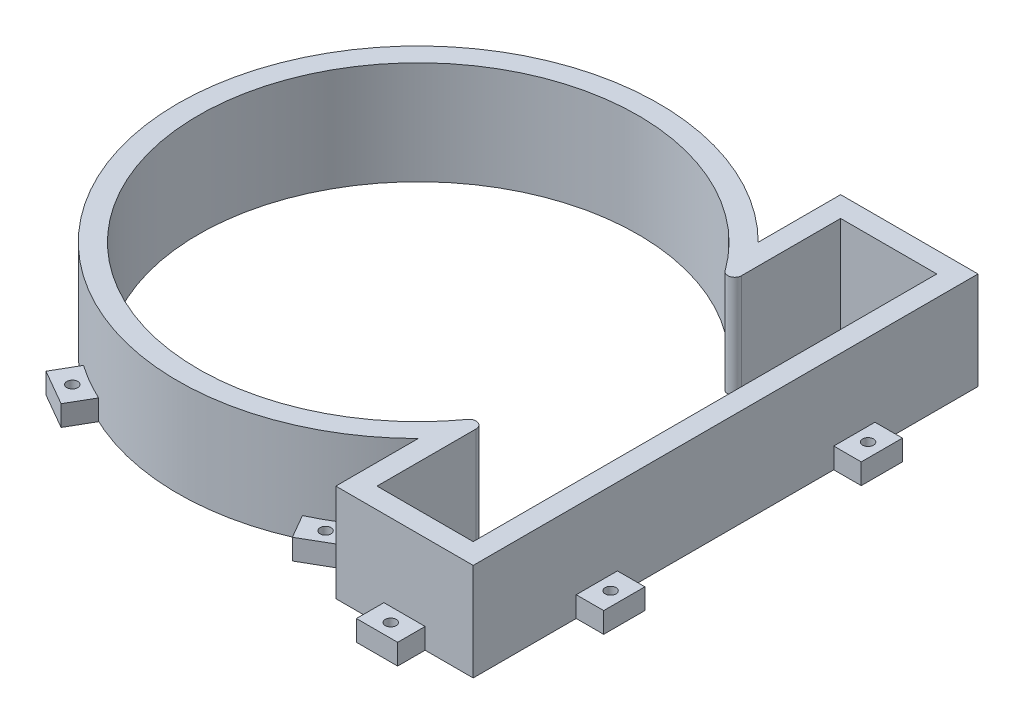
SolidWorks part; units mm, degrees
ref_plane "Front Plane" through (0, 0, 0) normal (0, 0, 1) x (1, 0, 0)
ref_plane "Top Plane" through (0, 0, 0) normal (0, 1, 0) x (1, 0, 0)
ref_plane "Right Plane" through (0, 0, 0) normal (1, 0, 0) x (0, 0, -1)
sketch "Sketch1" plane through (0, 0, 0) normal (0, 1, 0) x (1, 0, 0)
  line L0 (24.7487, 24.7487) -> (24.7487, 36.7487)
  line L1 (50, 50) -> (-50, 50) construction
  line L2 (50, 50) -> (50, -50) construction
  line L3 (50, -50) -> (-50, -50) construction
  line L4 (-50, 50) -> (-50, -50) construction
  line L5 (50, 50) -> (-50, -50) construction
  line L6 (50, -50) -> (-50, 50) construction
  line L7 (24.7487, 36.7487) -> (44.7487, 36.7487)
  line L8 (44.7487, 36.7487) -> (44.7487, -36.7487)
  line L9 (0, 0) -> (50, 0) construction
  line L10 (24.7487, -36.7487) -> (44.7487, -36.7487)
  line L11 (24.7487, -24.7487) -> (24.7487, -36.7487)
  line L12 (27.7487, -15.9376) -> (27.7487, -33.7487)
  line L13 (27.7487, -33.7487) -> (41.7487, -33.7487)
  line L14 (41.7487, 33.7487) -> (41.7487, -33.7487)
  line L15 (27.7487, 33.7487) -> (41.7487, 33.7487)
  line L16 (27.7487, 15.9376) -> (27.7487, 33.7487)
  arc A1 (24.7487, 24.7487) -> (24.7487, -24.7487) centre (0, 0) ccw
  arc A4 (27.7487, 15.9376) -> (27.7487, -15.9376) centre (0, 0) ccw
  point P0 (0, 0)
  point P13 (44.7487, 0)
  dimension "D3" = 70
  dimension "D6" = 3
  dimension "D1" = 100
  dimension "D2" = 100
  dimension "D4" = 12
  dimension "D5" = 20
extrude "Boss-Extrude1" add sketch "Sketch1" along normal blind 15
chamfer "Chamfer13" distance 3 angle 15 6 edges at (24.7487, 0, -30.7487) (34.7487, 0, -36.7487) (44.7487, 0, 0) (34.7487, 0, 36.7487) (24.7487, 0, 30.7487) (-35, 0, 0) first distance on face at (21.4573, 0, 0)
ref_plane "Plane3" through (0, 0.8038, 0) normal (0, -1, 0) x (-1, 0, 0)
sketch "Sketch6" plane through (0, 0.8038, 0) normal (0, -1, 0) x (-1, 0, 0)
  line L0 (-48.1424, 0) -> (38.8712, 0) construction
  line L1 (34.8712, -3) -> (38.8712, -3)
  line L2 (38.8712, -3) -> (38.8712, 3)
  line L3 (34.8712, 3) -> (38.8712, 3)
  line L4 (14.8375, -31.6993) -> (16.8375, -35.1634)
  line L5 (16.8375, -35.1634) -> (22.0337, -32.1634)
  line L6 (20.0337, -28.6993) -> (22.0337, -32.1634)
  line L7 (-20.0337, -28.6993) -> (-22.0337, -32.1634)
  line L8 (-22.0337, -32.1634) -> (-16.8375, -35.1634)
  line L9 (-14.8375, -31.6993) -> (-16.8375, -35.1634)
  line L10 (-34.7487, -36.7487) -> (-34.7487, -40.7487) construction
  line L11 (-24.7487, -36.7487) -> (-44.7487, -36.7487) construction
  line L12 (-44.7487, -18.7487) -> (-48.7487, -18.7487) construction
  line L13 (-14.8375, 31.6993) -> (-16.8375, 35.1634)
  line L14 (-16.8375, 35.1634) -> (-22.0337, 32.1634)
  line L15 (-20.0337, 28.6993) -> (-22.0337, 32.1634)
  line L16 (20.0337, 28.6993) -> (22.0337, 32.1634)
  line L17 (22.0337, 32.1634) -> (16.8375, 35.1634)
  line L18 (14.8375, 31.6993) -> (16.8375, 35.1634)
  line L19 (-34.8712, -3) -> (-38.8712, -3) [skipped]
  line L20 (-38.8712, 3) -> (-38.8712, 0) [skipped]
  line L21 (-34.8712, 3) -> (-38.8712, 3) [skipped]
  line L22 (-44.7487, -36.7487) -> (-44.7487, 36.7487) construction
  line L23 (-31.7487, -36.7487) -> (-31.7487, -40.7487)
  line L24 (-31.7487, -40.7487) -> (-37.7487, -40.7487)
  line L25 (-37.7487, -36.7487) -> (-37.7487, -40.7487)
  line L26 (-44.7487, -21.7487) -> (-48.7487, -21.7487)
  line L27 (-48.7487, -21.7487) -> (-48.7487, -15.7487)
  line L28 (-44.7487, -15.7487) -> (-48.7487, -15.7487)
  line L29 (-31.7487, -36.7487) -> (-37.7487, -36.7487)
  line L30 (-44.7487, -21.7487) -> (-44.7487, -15.7487)
  line L31 (-44.7487, 15.7487) -> (-48.7487, 15.7487)
  line L32 (-48.7487, 21.7487) -> (-48.7487, 15.7487)
  line L33 (-44.7487, 21.7487) -> (-44.7487, 15.7487)
  line L34 (-44.7487, 21.7487) -> (-48.7487, 21.7487)
  line L35 (-31.7487, 36.7487) -> (-37.7487, 36.7487)
  line L36 (-37.7487, 36.7487) -> (-37.7487, 40.7487)
  line L37 (-31.7487, 40.7487) -> (-37.7487, 40.7487)
  line L38 (-31.7487, 36.7487) -> (-31.7487, 40.7487)
  arc A0 (-20.0337, -28.6993) -> (-14.8375, -31.6993) centre (0, 0) ccw
  arc A1 (-24.7487, -24.7487) -> (-24.7487, 24.7487) centre (0, 0) ccw construction
  circle A2 centre (36.8712, 0) radius 0.795
  circle A3 centre (18.4356, -31.9314) radius 0.795
  circle A4 centre (-18.4356, -31.9314) radius 0.795
  circle A6 centre (-18.4356, 31.9314) radius 0.795
  circle A7 centre (18.4356, 31.9314) radius 0.795
  arc A8 (-37.6662, 0) -> (-36.0762, 0) centre (-36.8712, 0) ccw [skipped]
  circle A9 centre (-34.7487, -38.7487) radius 0.795
  circle A10 centre (-46.7487, -18.7487) radius 0.795
  circle A11 centre (-46.7487, 18.7487) radius 0.795
  circle A12 centre (-34.7487, 38.7487) radius 0.795
  arc A13 (-14.8375, 31.6993) -> (-20.0337, 28.6993) centre (0, 0) ccw
  arc A14 (20.0337, 28.6993) -> (14.8375, 31.6993) centre (0, 0) ccw
  arc A15 (34.8712, -3) -> (34.8712, 3) centre (0, 0) ccw
  arc A16 (14.8375, -31.6993) -> (20.0337, -28.6993) centre (0, 0) ccw
  point P47 (0, 0)
  dimension "D1" = 3
  dimension "D3" = 1.59
  dimension "D8" = 1.59
  dimension "D12" = 1.59
  dimension "D2" = 4
  dimension "D4" = 2
  dimension "D6" = 4
  dimension "D7" = 3
  dimension "D9" = 4
  dimension "D10" = 3
  dimension "D11" = 18
  dimension "D5" = 6
extrude "Boss-Extrude4" add sketch "Sketch6" against normal blind 3 separate body
fillet "Fillet1" radius 1 2 edges at (27.7487, 7.5, 15.9376) (27.7487, 7.5, -15.9376)
